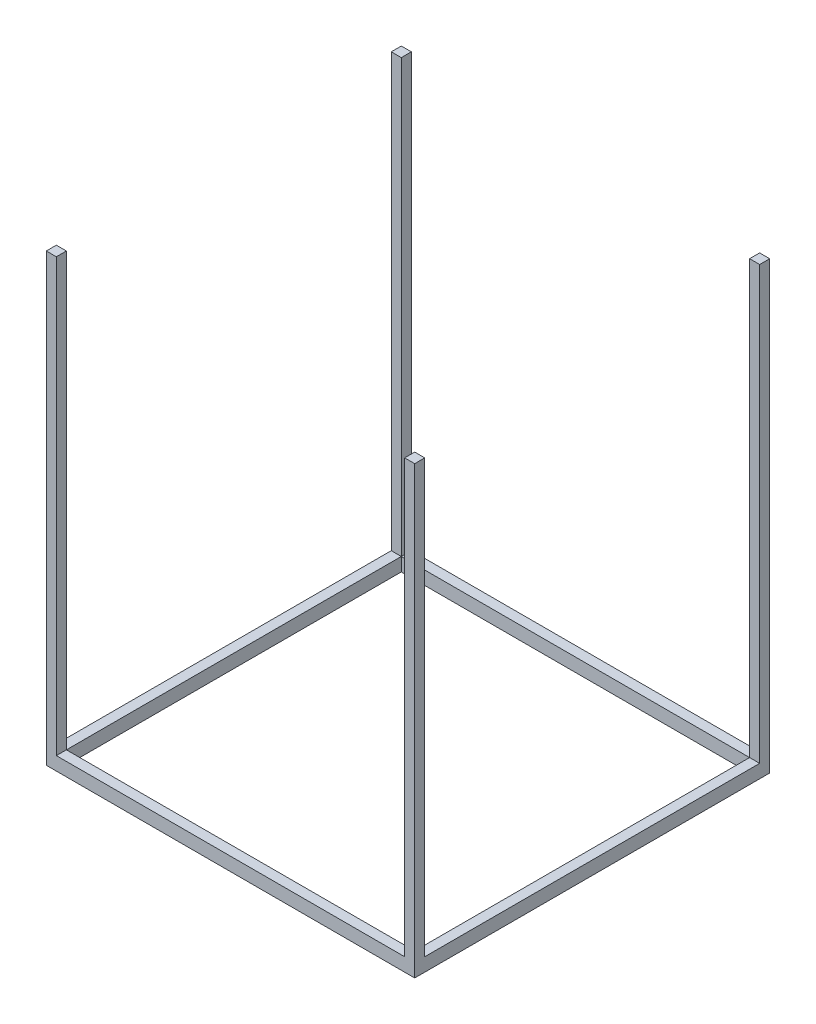
SolidWorks part; units mm, degrees
material "Galvanized Steel"
ref_plane "Front Plane" through (0, 0, 0) normal (0, 0, 1) x (1, 0, 0)
ref_plane "Top Plane" through (0, 0, 0) normal (0, 1, 0) x (1, 0, 0)
ref_plane "Right Plane" through (0, 0, 0) normal (1, 0, 0) x (0, 0, -1)
sketch "Sketch1" plane through (0, 0, 0) normal (0, 1, 0) x (1, 0, 0)
  line L0 (-660.4, 635) -> (-698.5, 635)
  line L1 (-698.5, -673.1) -> (698.5, -673.1)
  line L2 (-698.5, -673.1) -> (-698.5, 673.1)
  line L3 (-698.5, 673.1) -> (698.5, 673.1)
  line L4 (698.5, -673.1) -> (698.5, 673.1)
  line L5 (-698.5, -673.1) -> (698.5, 673.1) construction
  line L6 (-698.5, 673.1) -> (698.5, -673.1) construction
  line L7 (-660.4, -635) -> (660.4, -635)
  line L8 (-660.4, -635) -> (-660.4, 635)
  line L9 (-660.4, 635) -> (660.4, 635)
  line L10 (660.4, -635) -> (660.4, 635)
  line L11 (-660.4, -635) -> (660.4, 635) construction
  line L12 (-660.4, 635) -> (660.4, -635) construction
  line L13 (-660.4, 635) -> (-660.4, 673.1)
  line L14 (660.4, 635) -> (660.4, 673.1)
  line L15 (660.4, 635) -> (698.5, 635)
  line L16 (660.4, -635) -> (698.5, -635)
  line L17 (660.4, -635) -> (660.4, -673.1)
  line L18 (-660.4, -635) -> (-698.5, -635)
  line L19 (-660.4, -635) -> (-660.4, -673.1)
  point P0 (0, 0)
  point P6 (0, 0)
  dimension "D1" = 1320.8
  dimension "D2" = 1270
  dimension "D3" = 38.1
  dimension "D4" = 38.1
extrude "Boss-Extrude1" add sketch "Sketch1" along normal blind 50.8 contours L9 L14 L3 L13 | L18 L8 L0 L2 | L0 L13 L3 L2 | L19 L18 L2 L1 | L7 L19 L1 L17 | L16 L17 L1 L4 | L10 L16 L4 L15 | L14 L15 L4 L3 region at (-679.45, 0, 0) region at (0, 0, -654.05) region at (-679.45, 0, -654.05) region at (-679.45, 0, 654.05) region at (0, 0, 654.05) region at (679.45, 0, 0) region at (679.45, 0, -654.05) region at (679.45, 0, 654.05)
extrude "Boss-Extrude2" add sketch "Sketch1<3>" along normal blind 1689.1 contours L19 L18 L2 L1 | L0 L13 L3 L2 | L14 L15 L4 L3 | L16 L17 L1 L4 region at (-679.45, 0, -654.05) region at (-679.45, 0, 654.05) region at (679.45, 0, -654.05) region at (679.45, 0, 654.05)
sketch "Sketch1<3>" plane through (0, 0, 0) normal (0, 1, 0) x (1, 0, 0) same geometry as "Sketch1"
